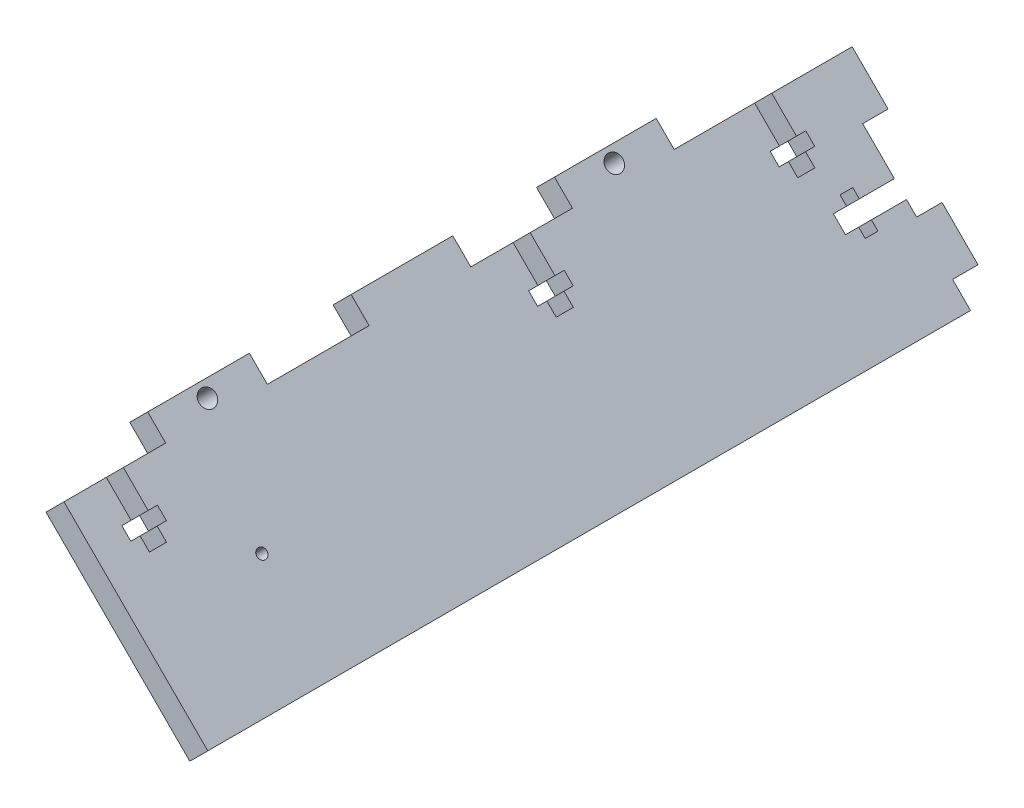
SolidWorks part; units mm, degrees
ref_plane "Front Plane" through (0, 0, 0) normal (0, 0, 1) x (1, 0, 0)
ref_plane "Top Plane" through (0, 0, 0) normal (0, 1, 0) x (1, 0, 0)
ref_plane "Right Plane" through (0, 0, 0) normal (1, 0, 0) x (0, 0, -1)
sketch "Sketch1" plane through (0, 0, 0) normal (0, 0, 1) x (1, 0, 0)
  line L0 (-105.5101, 43.1479) -> (-54.0999, -8.2622) construction
  line L1 (-17.576, -49.2763) -> (-60.6709, -6.1813) construction
  line L2 (-56.1808, -1.6912) -> (-13.0858, -44.7862) construction
  line L3 (-73.6381, 43.6049) -> (-37.7171, 7.6839)
  line L4 (-73.6381, 43.6049) -> (-69.148, 48.095)
  line L5 (-37.7171, 7.6839) -> (-33.2269, 12.174)
  line L6 (-69.148, 48.095) -> (-33.2269, 12.174)
  line L7 (-70.046, -24.645) -> (-105.967, 11.276) construction
  line L8 (-74.5361, -29.1352) -> (-70.046, -24.645) construction
extrude "Boss-Extrude1" add sketch "Sketch1" along normal up to surface (190.5 mm away)
sketch "Sketch2" plane through (-58.6215, 58.6215, 0) normal (-0.7071, 0.7071, 0) x (0, 0, 1)
  line L0 (190.5, -14.8867) -> (0, -14.8867) construction
  line L1 (165.1, -14.8867) -> (139.7, -14.8867)
  line L2 (165.1, -14.8867) -> (165.1, -21.2367)
  line L3 (165.1, -21.2367) -> (139.7, -21.2367)
  line L4 (139.7, -14.8867) -> (139.7, -21.2367)
  line L5 (190.5, -21.2367) -> (0, -21.2367) construction
  dimension "D1" = 25.4
  dimension "D2" = 25.4
extrude "Boss-Extrude2" add sketch "Sketch2" along normal blind 6.35
pattern_linear "LPattern1" count 3 spacing 50.8 along (0, 0, -1) of "Boss-Extrude2"
sketch "Sketch3" plane through (0, 0, 0) normal (0, 0, -1) x (-1, 0, 0)
  line L0 (73.6381, 43.6049) -> (64.6578, 34.6246)
  line L1 (73.6381, 43.6049) -> (37.7171, 7.6839) construction
  line L2 (64.6578, 34.6246) -> (60.1677, 39.1148)
  line L3 (33.2269, 12.174) -> (69.148, 48.095) construction
  line L4 (60.1677, 39.1148) -> (69.148, 48.095)
  line L5 (69.148, 48.095) -> (73.6381, 43.6049)
  dimension "D1" = 12.7
extrude "Boss-Extrude3" add sketch "Sketch3" along normal blind 6.35
pattern_linear "LPattern2" count 2 spacing 31.75 along (0.7071, -0.7071, 0) of "Boss-Extrude3"
sketch "Sketch4" plane through (-10.5265, -10.5265, 0) normal (0.7071, 0.7071, 0) x (0, 0, -1)
  circle A0 centre (-159.0375, 57.5033) radius 1.25
  dimension "D1" = 2.5
extrude "Cut-Extrude1" cut sketch "Sketch4" against normal through all
sketch "Sketch5" plane through (-10.5265, -10.5265, 0) normal (0.7071, 0.7071, 0) x (0, 0, -1)
  line L0 (-177.8, 82.9033) -> (-177.8, 68.4326) construction
  line L1 (-190.5, 82.9033) -> (-165.1, 82.9033) construction
  line L2 (-76.2, 82.9033) -> (-76.2, 62.5112) construction
  line L3 (-88.9, 82.9033) -> (-63.5, 82.9033) construction
  line L4 (-15.875, 82.9033) -> (-15.875, 66.2052) construction
  line L5 (-38.1, 82.9033) -> (6.35, 82.9033) construction
  line L6 (-38.1412, 82.9033) -> (0, 82.9033) construction
  line B0 (-175.6664, 82.9033) -> (-179.9336, 82.9033)
  line B1 (-179.9336, 70.9653) -> (-182.245, 70.9653)
  line B2 (-182.245, 70.9653) -> (-182.245, 74.1403)
  line B3 (-182.245, 74.1403) -> (-179.9336, 74.1403)
  line B4 (-179.9336, 74.1403) -> (-179.9336, 82.9033)
  line B5 (-179.9336, 70.9653) -> (-179.9336, 67.6633)
  line B6 (-179.9336, 67.6633) -> (-175.6664, 67.6633)
  line B7 (-175.6664, 70.9653) -> (-175.6664, 67.6633)
  line B8 (-175.6664, 74.1403) -> (-175.6664, 82.9033)
  line B9 (-173.355, 74.1403) -> (-175.6664, 74.1403)
  line B10 (-173.355, 70.9653) -> (-173.355, 74.1403)
  line B11 (-175.6664, 70.9653) -> (-173.355, 70.9653)
  line B12 (-74.0664, 82.9033) -> (-78.3336, 82.9033)
  line B13 (-78.3336, 70.9653) -> (-80.645, 70.9653)
  line B14 (-80.645, 70.9653) -> (-80.645, 74.1403)
  line B15 (-80.645, 74.1403) -> (-78.3336, 74.1403)
  line B16 (-78.3336, 74.1403) -> (-78.3336, 82.9033)
  line B17 (-78.3336, 70.9653) -> (-78.3336, 67.6633)
  line B18 (-78.3336, 67.6633) -> (-74.0664, 67.6633)
  line B19 (-74.0664, 70.9653) -> (-74.0664, 67.6633)
  line B20 (-74.0664, 74.1403) -> (-74.0664, 82.9033)
  line B21 (-71.755, 74.1403) -> (-74.0664, 74.1403)
  line B22 (-71.755, 70.9653) -> (-71.755, 74.1403)
  line B23 (-74.0664, 70.9653) -> (-71.755, 70.9653)
  line B24 (-13.7414, 82.9033) -> (-18.0086, 82.9033)
  line B25 (-18.0086, 70.9653) -> (-20.32, 70.9653)
  line B26 (-20.32, 70.9653) -> (-20.32, 74.1403)
  line B27 (-20.32, 74.1403) -> (-18.0086, 74.1403)
  line B28 (-18.0086, 74.1403) -> (-18.0086, 82.9033)
  line B29 (-18.0086, 70.9653) -> (-18.0086, 67.6633)
  line B30 (-18.0086, 67.6633) -> (-13.7414, 67.6633)
  line B31 (-13.7414, 70.9653) -> (-13.7414, 67.6633)
  line B32 (-13.7414, 74.1403) -> (-13.7414, 82.9033)
  line B33 (-11.43, 74.1403) -> (-13.7414, 74.1403)
  line B34 (-11.43, 70.9653) -> (-11.43, 74.1403)
  line B35 (-13.7414, 70.9653) -> (-11.43, 70.9653)
sketch_block_instance "TSlot-1"
sketch_block "TSlot" parameters "D1"=3.302, "D2"=3.175
sketch_block_instance "TSlot-2"
sketch_block_instance "TSlot-3"
extrude "Cut-Extrude2" cut sketch "Sketch5" against normal through all
sketch "Sketch6" plane through (-15.0166, -15.0166, 0) normal (-0.7071, -0.7071, 0) x (0, 0, 1)
  line L0 (150.287, 89.2533) -> (154.5542, 82.9033) construction
  line L1 (139.7, 89.2533) -> (165.1, 89.2533) construction
  line L2 (150.287, 89.2533) -> (150.287, 82.9033) construction
  line L3 (154.5542, 89.2533) -> (150.287, 82.9033) construction
  line L4 (154.5542, 82.9033) -> (154.5542, 89.2533) construction
  line L5 (48.687, 89.2533) -> (52.9542, 82.9033) construction
  line L6 (38.1, 89.2533) -> (63.5, 89.2533) construction
  line L7 (48.687, 89.2533) -> (48.687, 82.9033) construction
  line L8 (52.9542, 89.2533) -> (48.687, 82.9033) construction
  line L9 (52.9542, 82.9033) -> (52.9542, 89.2533) construction
  circle A0 centre (152.4206, 86.0783) radius 2.0955
  circle A1 centre (50.8206, 86.0783) radius 2.0955
  dimension "D1" = 4.191
extrude "Cut-Extrude3" cut sketch "Sketch6" against normal through all
sketch "Sketch7" plane through (-10.5265, -10.5265, 0) normal (0.7071, 0.7071, 0) x (0.7071, -0.7071, 0)
  line L0 (-56.8683, 0) -> (-56.8683, -24.4742) construction
  line L1 (-51.1533, 0) -> (-70.2033, 0) construction
  line L4 (-67.6633, -18.0086) -> (-67.6633, -13.7414) construction
  line B0 (-54.7347, 0) -> (-59.0019, 0)
  line B1 (-59.0019, -11.938) -> (-61.3133, -11.938)
  line B2 (-61.3133, -11.938) -> (-61.3133, -8.763)
  line B3 (-61.3133, -8.763) -> (-59.0019, -8.763)
  line B4 (-59.0019, -8.763) -> (-59.0019, 0)
  line B5 (-59.0019, -11.938) -> (-59.0019, -15.24)
  line B6 (-59.0019, -15.24) -> (-54.7347, -15.24)
  line B7 (-54.7347, -11.938) -> (-54.7347, -15.24)
  line B8 (-54.7347, -8.763) -> (-54.7347, 0)
  line B9 (-52.4233, -8.763) -> (-54.7347, -8.763)
  line B10 (-52.4233, -11.938) -> (-52.4233, -8.763)
  line B11 (-54.7347, -11.938) -> (-52.4233, -11.938)
  dimension "D1" = 6.35
sketch_block_instance "TSlot-4"
extrude "Cut-Extrude4" cut sketch "Sketch7" against normal through all
